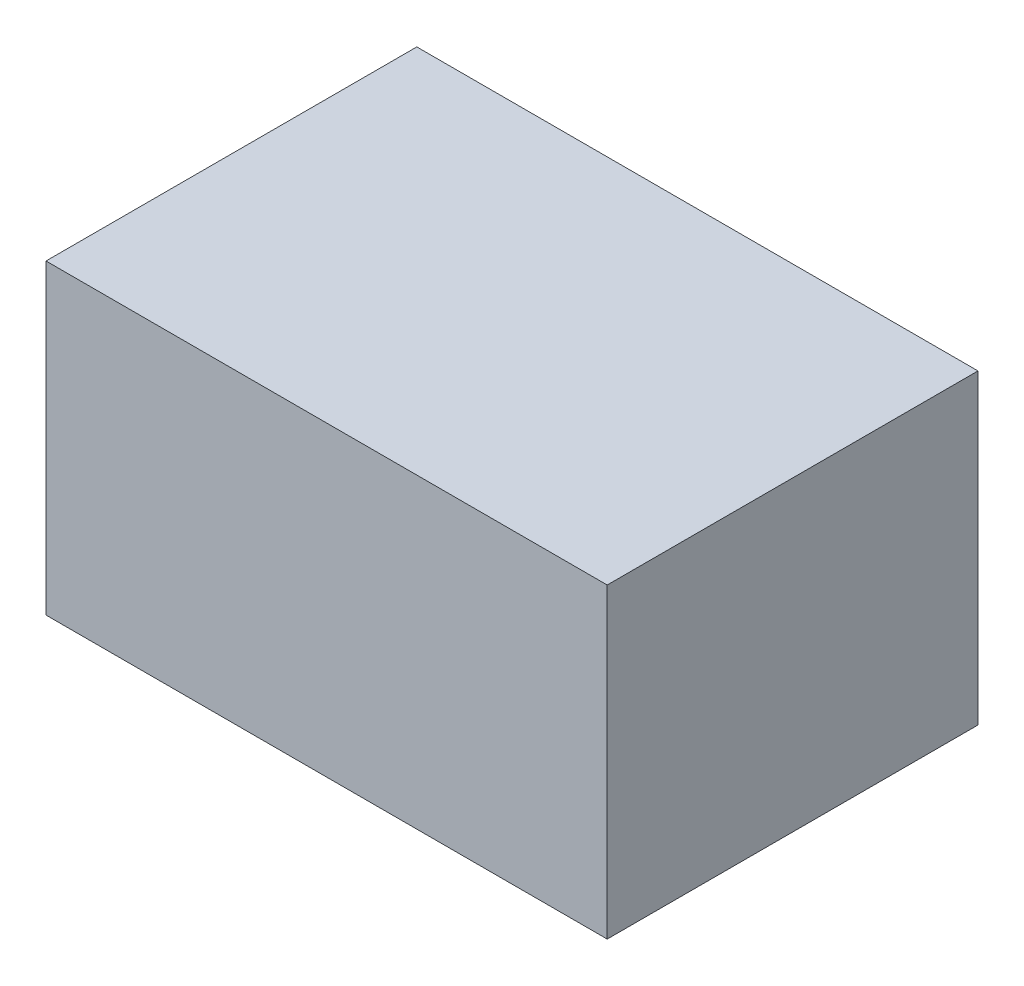
SolidWorks part; units mm, degrees
ref_plane "Front Plane" through (0, 0, 0) normal (0, 0, 1) x (1, 0, 0)
ref_plane "Top Plane" through (0, 0, 0) normal (0, 1, 0) x (1, 0, 0)
ref_plane "Right Plane" through (0, 0, 0) normal (1, 0, 0) x (0, 0, -1)
sketch "Sketch1" plane through (0, 0, 0) normal (0, 1, 0) x (1, 0, 0)
  line L1 (-355.6, -234.95) -> (355.6, -234.95)
  line L2 (-355.6, -234.95) -> (-355.6, 234.95)
  line L3 (-355.6, 234.95) -> (355.6, 234.95)
  line L4 (355.6, -234.95) -> (355.6, 234.95)
  line L5 (-355.6, -234.95) -> (355.6, 234.95) construction
  line L6 (-355.6, 234.95) -> (355.6, -234.95) construction
  point P0 (0, 0)
  dimension "D1" = 711.2
  dimension "D2" = 469.9
extrude "Boss-Extrude1" add sketch "Sketch1" along normal blind 388.62 contours L2 L3 L4 L1
